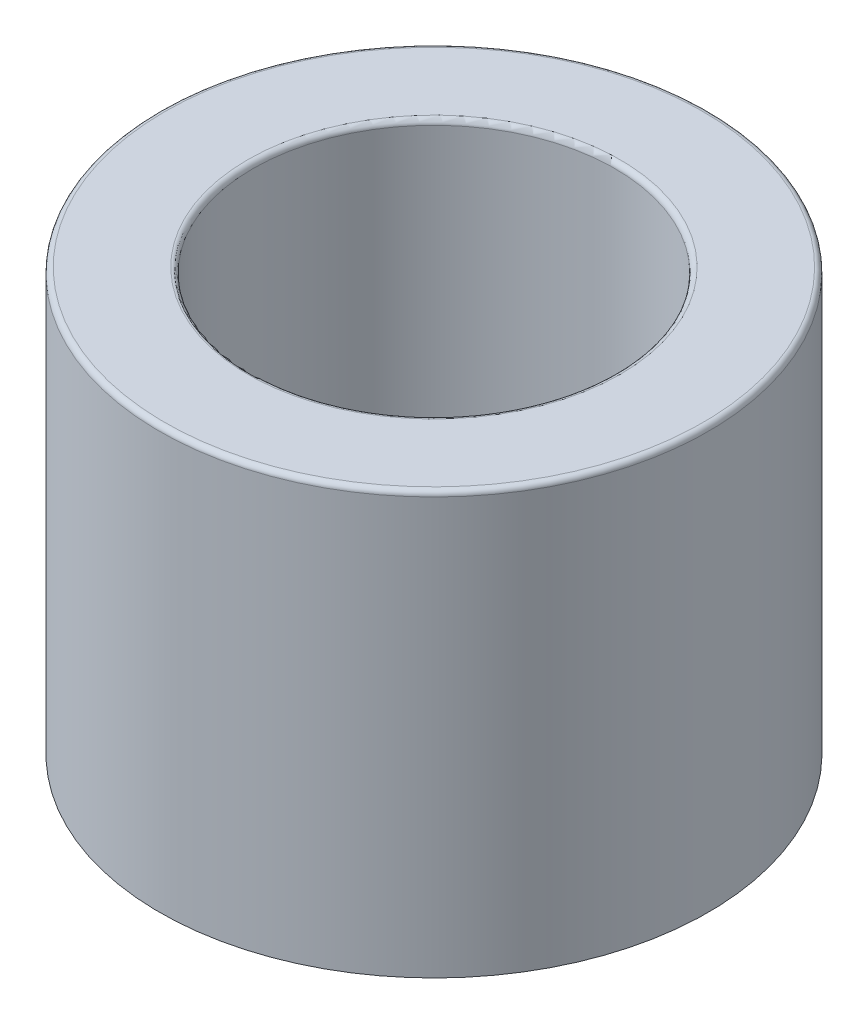
SolidWorks part; units mm, degrees
ref_plane "Front" through (0, 0, 0) normal (0, 0, 1) x (1, 0, 0)
ref_plane "Top" through (0, 0, 0) normal (0, 1, 0) x (1, 0, 0)
ref_plane "Right" through (0, 0, 0) normal (1, 0, 0) x (0, 0, -1)
sketch "Sketch1" plane through (0, 0, 0) normal (0, 0, 1) x (1, 0, 0)
  line L0 (7.1437, -4.7625) -> (-7.1437, -4.7625) construction
  line L1 (0, -4.7625) -> (0, 4.7625) construction
  line L2 (4.7625, -0.7938) -> (-4.7625, -0.7938) construction
  line L3 (2.3813, -4.7625) -> (-2.3813, -4.7625) construction
  point P7 (0, -0.7938)
  dimension "OD" = 14.2875
  dimension "Height" = 9.525
  dimension "Counterbore Diameter" = 9.525
  dimension "Mounting Surface Height" = 3.9688
  dimension "Mounting Hole Diameter" = 4.7625
sketch "Sketch2" plane through (0, 0, 0) normal (0, 0, 1) x (1, 0, 0)
  line L0 (-7.3438, -4.8898) -> (-7.3438, 6.7625)
  line L1 (-7.3438, 6.7625) -> (-4.7625, 6.7625)
  line L2 (-4.7625, 6.7625) -> (-4.7625, -0.7938)
  line L3 (-4.7625, -0.7938) -> (0.2375, -0.7938)
  line L4 (4.7625, -0.7938) -> (-4.7625, -0.7938) construction
  line L5 (0.2375, -0.7938) -> (0.2375, -4.8898)
  line L6 (0.2375, -4.8898) -> (-7.3438, -4.8898)
  dimension "D1" = 4.096
  dimension "D2" = 5
  dimension "D3" = 2.5812
  dimension "D4" = 7.5812
  dimension "D5" = 11.6523
revolve "Revolve1" add sketch "Sketch2" angle 360 about L5
ref_axis "Axis1" through (0.2375, -4.8898, 0) along (0, 1, 0)
fillet "Fillet1" radius 0.1429 2 edges at (-4.7625, 6.7625, 0) (-7.3438, 6.7625, 0)
equation "\"D1@Fillet1\"=\"OD@Sketch1\"*.01"
